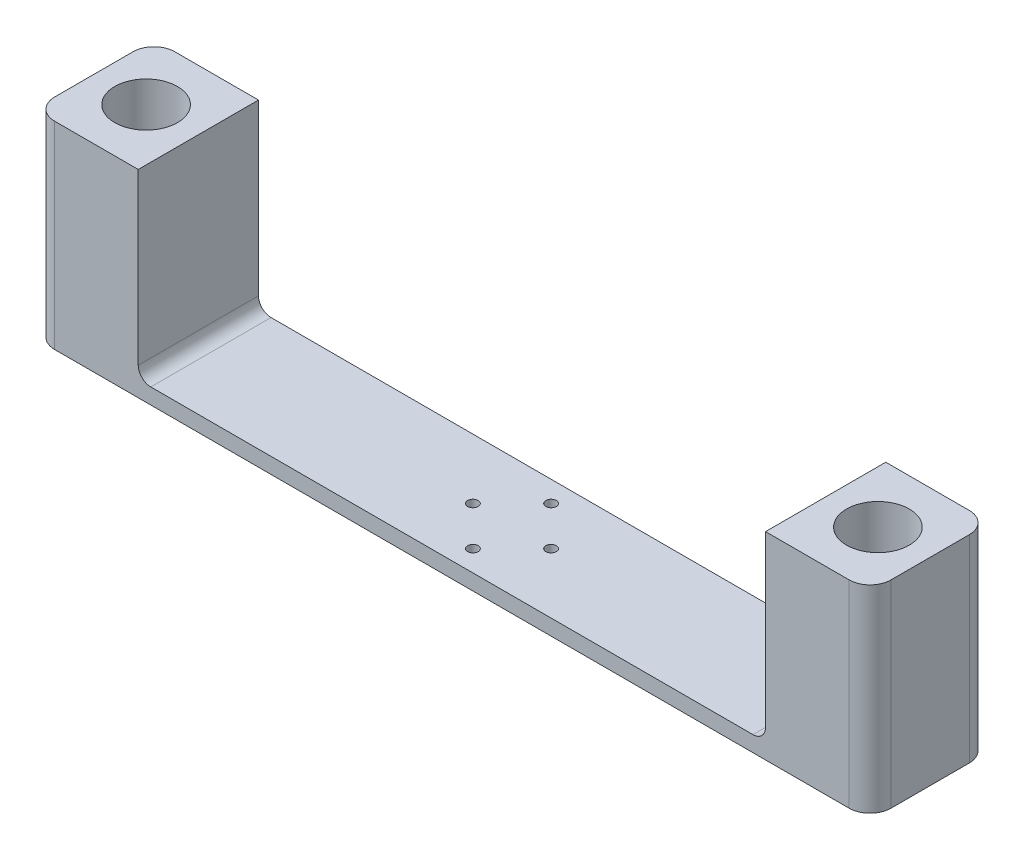
SolidWorks part; units mm, degrees
ref_plane "Front Plane" through (0, 0, 0) normal (0, 0, 1) x (1, 0, 0)
ref_plane "Top Plane" through (0, 0, 0) normal (0, 1, 0) x (1, 0, 0)
ref_plane "Right Plane" through (0, 0, 0) normal (1, 0, 0) x (0, 0, -1)
sketch "Sketch1" plane through (0, 0, 0) normal (0, 1, 0) x (1, 0, 0)
  line L0 (0, 0) -> (0, 4.9523) construction
  line L1 (0, 4.9523) -> (0, 0) construction
  line L2 (0, 0) -> (2.8355, 0) construction
  circle A0 centre (0, 0) radius 13.97
  circle A2 centre (0, 9.5) radius 1.275
  circle A3 centre (9.5, 0) radius 1.275
  circle A4 centre (0, -9.5) radius 1.275
  circle A5 centre (-9.5, 0) radius 1.275
  dimension "D2" = 27.94
  dimension "D3" = 2.55
extrude "Boss-Extrude1" add sketch "Sketch1" along normal blind 3.048
sketch "Sketch2" plane through (0, 3.048, 0) normal (0, 1, 0) x (1, 0, 0)
  line L1 (-96.52, -14.605) -> (96.52, -14.605)
  line L2 (-101.6, -9.525) -> (-101.6, 9.525)
  line L3 (-96.52, 14.605) -> (96.52, 14.605)
  line L4 (101.6, -9.525) -> (101.6, 9.525)
  line L5 (-101.6, -14.605) -> (101.6, 14.605) construction
  line L6 (-101.6, 14.605) -> (101.6, -14.605) construction
  circle A0 centre (-88.9, 0) radius 7.62
  circle A1 centre (88.9, 0) radius 7.62
  arc A3 (96.52, 14.605) -> (101.6, 9.525) centre (96.52, 9.525) cw
  arc A4 (96.52, -14.605) -> (101.6, -9.525) centre (96.52, -9.525) ccw
  arc A5 (-96.52, -14.605) -> (-101.6, -9.525) centre (-96.52, -9.525) cw
  arc A6 (-101.6, 9.525) -> (-96.52, 14.605) centre (-96.52, 9.525) cw
  circle A7 centre (9.5, 0) radius 1.275 construction
  circle A8 centre (0, 9.5) radius 1.275 construction
  circle A9 centre (-9.5, 0) radius 1.275 construction
  circle A10 centre (0, -9.5) radius 1.275 construction
  circle A11 centre (9.5, 0) radius 1.275
  circle A12 centre (0, 9.5) radius 1.275
  circle A13 centre (-9.5, 0) radius 1.275
  circle A14 centre (0, -9.5) radius 1.275
  point P0 (0, 0)
  dimension "D2" = 15.24
  dimension "D3" = 15.24
  dimension "D8" = 5.08
  dimension "D1" = 29.21
  dimension "D4" = 88.9
  dimension "D6" = 12.7
  dimension "D7" = 12.7
extrude "Boss-Extrude2" add sketch "Sketch2" along normal blind 45 and the other way through all
sketch "Sketch5" plane through (0, 0, -14.605) normal (0, 0, -1) x (-1, 0, 0)
  line L0 (-101.6, 0) -> (-101.6, 48.048)
  line L1 (-101.6, 48.048) -> (-76.2, 48.048)
  line L2 (-96.52, 48.048) -> (96.52, 48.048) construction
  line L3 (-76.2, 48.048) -> (-76.2, 3.81)
  line L4 (-76.2, 3.81) -> (76.2, 3.81)
  line L5 (0, 3.81) -> (0, 0)
  line L6 (101.6, 0) -> (-101.6, 0)
  line L7 (76.2, 48.048) -> (76.2, 3.81)
  line L8 (101.6, 48.048) -> (76.2, 48.048)
  line L9 (101.6, 0) -> (101.6, 48.048)
  line M8 (96.52, 48.048) -> (-96.52, 48.048)
  dimension "D1" = 25.4
  dimension "D2" = 3.81
extrude "Cut-Extrude2" cut sketch "Sketch5" against normal through all contours L7 L3 L4 M8 region at (0, 25.929, -14.605)
sketch "Sketch6" plane through (0, 0, 0) normal (0, -1, 0) x (1, 0, 0)
  circle A0 centre (-88.9, 0) radius 8.89
  circle A1 centre (-88.9, 0) radius 4.445
  circle A2 centre (88.9, 0) radius 8.89
  circle A3 centre (88.9, 0) radius 4.445
  dimension "D1" = 8.89
  dimension "D2" = 8.89
extrude "Boss-Extrude3" add sketch "Sketch6" against normal blind 4.572
fillet "Fillet2" radius 3.048 2 edges at (76.2, 3.81, 0) (-76.2, 3.81, 0)
sketch "Sketch10" plane through (0, 3.81, 0) normal (0, 1, 0) x (1, 0, 0)
  point P0 (0, 0)
